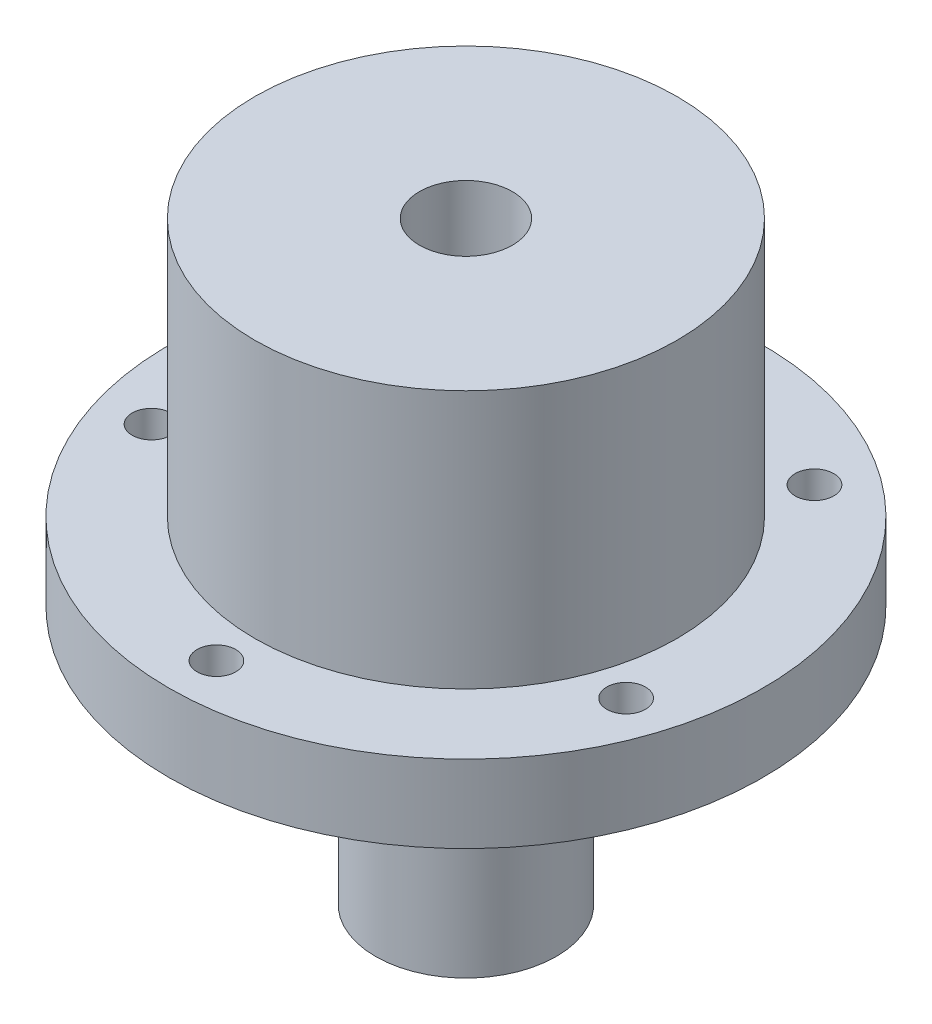
SolidWorks part; units mm, degrees
ref_plane "Front Plane" through (0, 0, 0) normal (0, 0, 1) x (1, 0, 0)
ref_plane "Top Plane" through (0, 0, 0) normal (0, 1, 0) x (1, 0, 0)
ref_plane "Right Plane" through (0, 0, 0) normal (1, 0, 0) x (0, 0, -1)
sketch "Sketch1" plane through (0, 0, 0) normal (0, 1, 0) x (1, 0, 0)
  circle A0 centre (0, 0) radius 1.8
  circle A1 centre (0, 0) radius 8.175
  circle A2 centre (0, 0) radius 11.5
  point P25 (0, 0)
extrude "Boss-Extrude1" add sketch "Sketch1" along normal blind 10 and the other way blind 3 contours A1 A0 region at (-7.9438, 0, 0)
extrude "Boss-Extrude2" add sketch "Sketch1<3>" against normal blind 3 separate body contours A2 A1 region at (-11.1747, 0, 0)
sketch "Sketch1<3>" plane through (0, 0, 0) normal (0, 1, 0) x (1, 0, 0) same geometry as "Sketch1"
sketch "Sketch2" plane through (0, 0, 0) normal (1, 0, 0) x (0, 0, -1)
  circle A0 centre (0, 4.7029) radius 1.25
  point P2 (0, 4.7029)
extrude "Cut-Extrude1" cut sketch "Sketch2" against normal blind 15
sketch "Sketch3" plane through (0, -3, 0) normal (0, -1, 0) x (1, 0, 0)
  circle A0 centre (0, 9.6613) radius 0.75
  circle A2 centre (9.1884, 2.9855) radius 0.75
  circle A3 centre (5.6787, -7.8161) radius 0.75
  circle A4 centre (-5.6787, -7.8161) radius 0.75
  circle A5 centre (-9.1884, 2.9855) radius 0.75
  point P2 (0, 0)
  point P3 (0, 0)
  point P4 (0, 9.6613)
  point P14 (0, 0)
  dimension "D1" = 5
sketch "Sketch4" plane through (0, -3, 0) normal (0, -1, 0) x (1, 0, 0)
  circle A0 centre (0, 0) radius 3.5
extrude "Boss-Extrude3" add sketch "Sketch4" along normal blind 10 contours A0
extrude "Cut-Extrude2" cut sketch "Sketch1<7>" against normal blind 13 contours A0
sketch "Sketch1<7>" plane through (0, 0, 0) normal (0, 1, 0) x (1, 0, 0) same geometry as "Sketch1"
extrude "Cut-Extrude3" cut sketch "Sketch3" against normal blind 10
